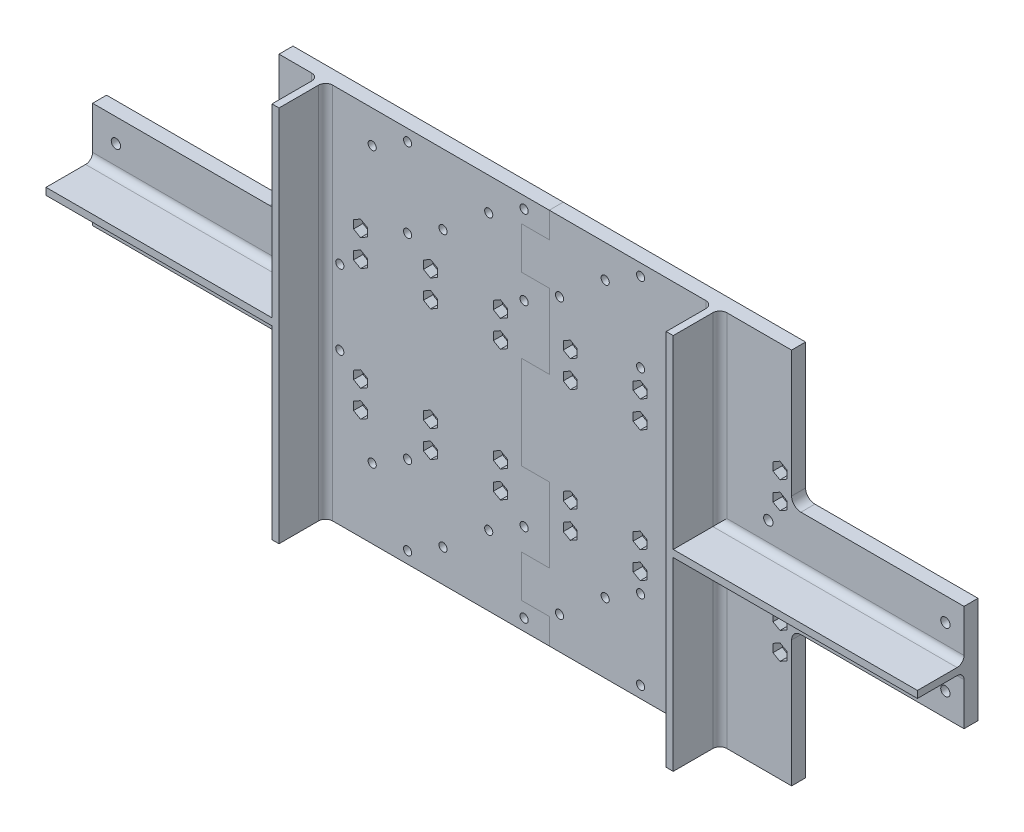
SolidWorks part; units mm, degrees
ref_plane "Top Plane" through (0, 0, 0) normal (0, 0, 1) x (1, 0, 0)
ref_plane "Right Plane" through (0, 0, 0) normal (0, 1, 0) x (1, 0, 0)
ref_plane "Front Plane" through (0, 0, 0) normal (1, 0, 0) x (0, 0, -1)
sketch "Sketch1" plane through (0, 0, 0) normal (0, 0, 1) x (1, 0, 0)
  line L0 (-187, 81) -> (187, -81) construction
  line L1 (-187, 81) -> (187, 81) construction
  line L2 (-187, 81) -> (-187, -81) construction
  line L3 (-187, -81) -> (187, -81) construction
  line L4 (187, 81) -> (187, -81) construction
  line L5 (-187, -22.75) -> (-107, -22.75) construction
  line L6 (-107, -22.75) -> (-107, -81) construction
  line L7 (113, -81) -> (113, -22.75) construction
  line L8 (113, -22.75) -> (187, -22.75) construction
  line L9 (-187, 0) -> (187, 0) construction
  line L10 (113, 22.75) -> (187, 22.75) construction
  line L11 (113, 81) -> (113, 22.75) construction
  line L12 (-107, 22.75) -> (-107, 81) construction
  line L13 (-187, 22.75) -> (-107, 22.75) construction
  line L14 (85.2, -81) -> (85.2, 81) construction
  line L15 (-93, -81) -> (-93, 81) construction
  line L16 (-187, -2.75) -> (187, -2.75) construction
  line L17 (187, 2.75) -> (-187, 2.75) construction
  text T0 "FRONT" font "Century Gothic" height in points 80
  dimension "D1" = 374
  dimension "D2" = 162
  dimension "D3" = 45.5
  dimension "D4" = 80
  dimension "D5" = 74
  dimension "D6" = 27.8
  dimension "D7" = 14
  dimension "D8" = 20
  dimension "D9" = 20
sketch "Sketch2" plane through (0, 0, 0) normal (0, 0, 1) x (1, 0, 0)
  line L0 (-187, 81) -> (-187, -81) construction
  line L1 (-187, 81) -> (187, 81) construction
  line L2 (187, 81) -> (187, -81) construction
  line L3 (-187, -81) -> (187, -81) construction
  line L4 (113, -81) -> (113, -22.75) construction
  line L5 (113, -22.75) -> (187, -22.75) construction
  line L6 (113, 22.75) -> (187, 22.75) construction
  line L7 (113, 81) -> (113, 22.75) construction
  line L8 (-107, 22.75) -> (-107, 81) construction
  line L9 (-187, 22.75) -> (-107, 22.75) construction
  line L10 (-107, -22.75) -> (-107, -81) construction
  line L11 (-187, -22.75) -> (-107, -22.75) construction
  line L12 (-187, 22.75) -> (-187, -22.75)
  line L13 (-107, 81) -> (113, 81)
  line L14 (187, 22.75) -> (187, -22.75)
  line L15 (-107, -81) -> (113, -81)
  line L16 (113, -81) -> (113, -22.75)
  line L17 (113, -22.75) -> (187, -22.75)
  line L18 (113, 22.75) -> (187, 22.75)
  line L19 (113, 81) -> (113, 22.75)
  line L20 (-107, 22.75) -> (-107, 81)
  line L21 (-187, 22.75) -> (-107, 22.75)
  line L22 (-107, -22.75) -> (-107, -81)
  line L23 (-187, -22.75) -> (-107, -22.75)
extrude "Boss-Extrude1" add sketch "Sketch2" along normal mid plane 6
sketch "Sketch3" plane through (0, 0, 3) normal (0, 0, 1) x (1, 0, 0)
  line L0 (-187, -1.5) -> (-90, -1.5)
  line L1 (-187, 81) -> (-187, -81) construction
  line L2 (187, 81) -> (187, -81) construction
  line L3 (-187, 0) -> (187, 0) construction
  line L4 (-187, 0) -> (187, 0) construction
  line L5 (-187, 1.5) -> (-90, 1.5)
  line L6 (-90, 81) -> (-90, 1.5)
  line L7 (-187, 81) -> (187, 81) construction
  line L8 (82.2, -81) -> (82.2, -1.5)
  line L9 (85.2, -81) -> (85.2, 81) construction
  line L10 (-93, -81) -> (-93, 81) construction
  line L11 (-87, -81) -> (-87, 81)
  line L12 (-187, -81) -> (187, -81) construction
  line L13 (79.2, -81) -> (79.2, 81)
  line L14 (79.2, -81) -> (82.2, -81)
  line L15 (79.2, 81) -> (82.2, 81)
  line L16 (-90, 81) -> (-87, 81)
  line L17 (-90, -81) -> (-87, -81)
  line L20 (82.2, 1.5) -> (187, 1.5)
  line L21 (82.2, -1.5) -> (187, -1.5)
  line L22 (82.2, 1.5) -> (82.2, 81)
  line L23 (-90, -1.5) -> (-90, -81)
  line L24 (187, -1.5) -> (187, 1.5)
  line L25 (-187, -1.5) -> (-187, 1.5)
  point P20 (0, 0)
  point P34 (-87, 0)
  point P35 (79.2, 0)
  dimension "D1" = 3
  dimension "D2" = 3
  dimension "D3" = 3
  dimension "D4" = 3
extrude "Boss-Extrude2" add sketch "Sketch3" along normal blind 20
sketch "Sketch4" plane through (0, 0, 3) normal (0, 0, 1) x (1, 0, 0)
  line L0 (-17, -67) -> (13.4, -67) construction
  line L1 (-67, -67) -> (-36.6, -67) construction
  line L2 (-67, -67) -> (-67, -51) construction
  line L3 (-67, -51) -> (-36.6, -51) construction
  line L4 (-36.6, -67) -> (-36.6, -51) construction
  line L5 (-17, -67) -> (-17, -51) construction
  line L6 (-17, -51) -> (13.4, -51) construction
  line L7 (13.4, -67) -> (13.4, -51) construction
  line L8 (33, -67) -> (63.4, -67) construction
  line L9 (33, -67) -> (33, -51) construction
  line L10 (33, -51) -> (63.4, -51) construction
  line L11 (63.4, -67) -> (63.4, -51) construction
  line L12 (-36.6, -67) -> (13.4, -67) construction
  line L13 (-107, -22.75) -> (-107, -81) construction
  line L14 (-67, 59) -> (63.4, 59) construction
  line L15 (-187, -81) -> (187, -81) construction
  line L16 (-187, 0) -> (187, 0) construction
  line L17 (-187, 0) -> (187, 0) construction
  line L18 (-36.6, 67) -> (13.4, 67) construction
  line L19 (63.4, 67) -> (63.4, 51) construction
  line L20 (33, 51) -> (63.4, 51) construction
  line L21 (33, 67) -> (33, 51) construction
  line L22 (33, 67) -> (63.4, 67) construction
  line L23 (13.4, 67) -> (13.4, 51) construction
  line L24 (-17, 51) -> (13.4, 51) construction
  line L25 (-17, 67) -> (-17, 51) construction
  line L26 (-36.6, 67) -> (-36.6, 51) construction
  line L27 (-67, 51) -> (-36.6, 51) construction
  line L28 (-67, 67) -> (-67, 51) construction
  line L29 (-67, 67) -> (-36.6, 67) construction
  line L30 (-17, 67) -> (13.4, 67) construction
  circle A0 centre (-36.6, -67) radius 1.75
  circle A1 centre (-67, -51) radius 1.75
  circle A2 centre (13.4, -67) radius 1.75
  circle A3 centre (-17, -51) radius 1.75
  circle A4 centre (63.4, -67) radius 1.75
  circle A5 centre (33, -51) radius 1.75
  circle A6 centre (33, 51) radius 1.75 construction
  circle A7 centre (63.4, 67) radius 1.75 construction
  circle A8 centre (-17, 51) radius 1.75 construction
  circle A9 centre (13.4, 67) radius 1.75 construction
  circle A10 centre (-67, 51) radius 1.75 construction
  circle A11 centre (-36.6, 67) radius 1.75 construction
  circle A12 centre (33, 67) radius 1.75
  circle A13 centre (63.4, 51) radius 1.75
  circle A14 centre (13.4, 51) radius 1.75
  circle A15 centre (-17, 67) radius 1.75
  circle A16 centre (-36.6, 51) radius 1.75
  circle A17 centre (-67, 67) radius 1.75
  dimension "D3" = 3.5
  dimension "D1" = 16
  dimension "D2" = 30.4
  dimension "D5" = 50
  dimension "D6" = 40
  dimension "D7" = 14
  dimension "D4" = 3
extrude "Cut-Extrude1" cut sketch "Sketch4" against normal through all
fillet "Fillet1" radius 4 4 edges at (-107, 22.75, 0) (-107, -22.75, 0) (113, -22.75, 0) (113, 22.75, 0)
fillet "Fillet2" radius 3 10 edges at (-90, 41.25, 3) (-138.5, 1.5, 3) (-138.5, -1.5, 3) (-90, -41.25, 3) (82.2, -41.25, 3) (134.6, -1.5, 3) (134.6, 1.5, 3) (82.2, 41.25, 3) (-87, 0, 3) (79.2, 0, 3)
sketch "Sketch5" plane through (0, 0, -3) normal (0, 0, -1) x (-1, 0, 0)
  circle A0 centre (-103, -12.75) radius 2 construction
  circle A1 centre (-103, 12.75) radius 2 construction
  circle A2 centre (-179, 12.75) radius 2 construction
  circle A3 centre (-179, -12.75) radius 2 construction
  circle A4 centre (177, 12.75) radius 2 construction
  circle A5 centre (177, -12.75) radius 2 construction
  circle A6 centre (101, -12.75) radius 2 construction
  circle A7 centre (101, 12.75) radius 2 construction
  circle A8 centre (-103, -12.75) radius 2
  circle A9 centre (-103, 12.75) radius 2
  circle A10 centre (-179, 12.75) radius 2
  circle A11 centre (-179, -12.75) radius 2
  circle A12 centre (177, 12.75) radius 2
  circle A13 centre (177, -12.75) radius 2
  circle A14 centre (101, -12.75) radius 2
  circle A15 centre (101, 12.75) radius 2
extrude "Cut-Extrude2" cut sketch "Sketch5" against normal up to next
sketch "Sketch6" plane through (0, 0, 3) normal (0, 0, 1) x (1, 0, 0)
  line L0 (-67, -67) -> (-36.6, -51) construction
  line L1 (-51.8, -76) -> (-51.8, -42) construction
  line L2 (-67, -59) -> (-36.6, -59) construction
  line L3 (-67, -67) -> (-67, -51) construction
  line L4 (-36.6, -67) -> (-36.6, -51) construction
  line L5 (-1.8, -76) -> (-1.8, -42) construction
  line L6 (48.2, -76) -> (48.2, -42) construction
  line L7 (-51.8, -59) -> (-1.8, -59) construction
  line L8 (-187, 0) -> (187, 0) construction
  line L9 (-187, 0) -> (187, 0) construction
  line L10 (-51.8, 59) -> (-1.8, 59) construction
  line L11 (48.2, 76) -> (48.2, 42) construction
  line L12 (-1.8, 76) -> (-1.8, 42) construction
  line L13 (-67, 59) -> (-36.6, 59) construction
  line L14 (-51.8, 76) -> (-51.8, 42) construction
  line L15 (-67, 67) -> (-36.6, 51) construction
  circle A0 centre (-51.8, -76) radius 1.75
  circle A1 centre (-51.8, -42) radius 1.75
  circle A2 centre (-1.8, -76) radius 1.75
  circle A3 centre (-1.8, -42) radius 1.75
  circle A4 centre (48.2, -76) radius 1.75
  circle A5 centre (48.2, -42) radius 1.75
  circle A6 centre (48.2, 42) radius 1.75
  circle A7 centre (48.2, 76) radius 1.75
  circle A8 centre (-1.8, 42) radius 1.75
  circle A9 centre (-1.8, 76) radius 1.75
  circle A10 centre (-51.8, 42) radius 1.75
  circle A11 centre (-51.8, 76) radius 1.75
  point P4 (-51.8, -59)
  point P17 (-1.8, -59)
  point P22 (48.2, -59)
  point P47 (48.2, 59)
  dimension "D1" = 3.5
  dimension "D2" = 34
  dimension "D4" = 50
  dimension "D3" = 3
extrude "Cut-Extrude3" cut sketch "Sketch6" against normal through all
sketch "Sketch8" plane through (0, 0, 3) normal (0, 0, 1) x (1, 0, 0)
  line L0 (-80.9, -16) -> (73.1, 16) construction
  line L1 (-80.9, -16) -> (73.1, -16) construction
  line L2 (-80.9, -16) -> (-80.9, 16) construction
  line L3 (-80.9, 16) -> (73.1, 16) construction
  line L4 (73.1, -16) -> (73.1, 16) construction
  line L5 (-187, 0) -> (187, 0) construction
  line L6 (-187, 0) -> (187, 0) construction
  line L7 (-3.9, -21.9049) -> (-3.9, 21.9049) construction
  line L8 (-93, -81) -> (85.2, 81) construction
  circle A0 centre (-80.9, -16) radius 1.75
  circle A1 centre (-80.9, 16) radius 1.75
  circle A2 centre (73.1, 16) radius 1.75
  circle A3 centre (73.1, -16) radius 1.75
  point P7 (-3.9, 0)
  dimension "D3" = 3.5
  dimension "D1" = 32
  dimension "D2" = 154
extrude "Cut-Extrude5" cut sketch "Sketch8" against normal through all
sketch "Sketch9" plane through (0, 0, 3) normal (0, 0, 1) x (1, 0, 0)
  line L0 (-107.9535, -28) -> (101.269, -28) construction
  line L1 (-12, -33.75) -> (18, -33.75) construction
  line L2 (-12, -22.25) -> (-42, -22.25) construction
  line L3 (-12, -22.25) -> (18, -22.25) construction
  line L4 (-194.5845, 0) -> (205.1662, 0) construction
  line L5 (3, -92.4344) -> (3, 92.4344) construction
  line L6 (-12, -33.75) -> (-42, -33.75) construction
  line L7 (-107, 81) -> (113, -81) construction
  line L8 (-45, -32.0179) -> (-45, -35.4821) construction
  line L9 (-15, -35.4821) -> (-12, -37.2141) construction
  line L10 (-12, -37.2141) -> (-9, -35.4821) construction
  line L11 (-9, -35.4821) -> (-9, -32.0179) construction
  line L12 (-9, -32.0179) -> (-12, -30.2859) construction
  line L13 (-12, -30.2859) -> (-15, -32.0179) construction
  line L14 (-15, -32.0179) -> (-15, -35.4821) construction
  line L15 (-45, -35.4821) -> (-42, -37.2141) construction
  line L16 (-42, -37.2141) -> (-39, -35.4821) construction
  line L17 (-39, -35.4821) -> (-39, -32.0179) construction
  line L18 (-39, -32.0179) -> (-42, -30.2859) construction
  line L19 (-42, -30.2859) -> (-45, -32.0179) construction
  line L20 (-75, -32.0179) -> (-75, -35.4821) construction
  line L21 (-75, -35.4821) -> (-72, -37.2141) construction
  line L22 (-72, -37.2141) -> (-69, -35.4821) construction
  line L23 (-69, -35.4821) -> (-69, -32.0179) construction
  line L24 (-69, -32.0179) -> (-72, -30.2859) construction
  line L25 (-72, -30.2859) -> (-75, -32.0179) construction
  line L26 (-105, -32.0179) -> (-105, -35.4821) construction
  line L27 (-105, -35.4821) -> (-102, -37.2141) construction
  line L28 (-102, -37.2141) -> (-99, -35.4821) construction
  line L29 (-99, -35.4821) -> (-99, -32.0179) construction
  line L30 (-99, -32.0179) -> (-102, -30.2859) construction
  line L31 (-102, -30.2859) -> (-105, -32.0179) construction
  line L32 (-45, -35.4821) -> (-39, -32.0179) construction
  line L33 (-42, -33.75) -> (-12, -33.75) construction
  line L34 (-12, -25.7141) -> (-15, -23.9821) construction
  line L35 (-9, -23.9821) -> (-12, -25.7141) construction
  line L36 (-9, -20.5179) -> (-9, -23.9821) construction
  line L37 (-12, -18.7859) -> (-9, -20.5179) construction
  line L38 (-15, -20.5179) -> (-12, -18.7859) construction
  line L39 (-15, -23.9821) -> (-15, -20.5179) construction
  line L40 (-39, -20.5179) -> (-39, -23.9821) construction
  line L41 (-42, -18.7859) -> (-39, -20.5179) construction
  line L42 (-45, -20.5179) -> (-42, -18.7859) construction
  line L43 (-45, -23.9821) -> (-45, -20.5179) construction
  line L44 (-42, -25.7141) -> (-45, -23.9821) construction
  line L45 (-39, -23.9821) -> (-42, -25.7141) construction
  line L46 (-69, -20.5179) -> (-69, -23.9821) construction
  line L47 (-72, -18.7859) -> (-69, -20.5179) construction
  line L48 (-75, -20.5179) -> (-72, -18.7859) construction
  line L49 (-75, -23.9821) -> (-75, -20.5179) construction
  line L50 (-72, -25.7141) -> (-75, -23.9821) construction
  line L51 (-69, -23.9821) -> (-72, -25.7141) construction
  line L52 (-99, -20.5179) -> (-99, -23.9821) construction
  line L53 (-102, -18.7859) -> (-99, -20.5179) construction
  line L54 (-105, -20.5179) -> (-102, -18.7859) construction
  line L55 (-105, -23.9821) -> (-105, -20.5179) construction
  line L56 (-102, -25.7141) -> (-105, -23.9821) construction
  line L57 (-99, -23.9821) -> (-102, -25.7141) construction
  line L58 (105, -23.9821) -> (108, -25.7141) construction
  line L59 (108, -25.7141) -> (111, -23.9821) construction
  line L60 (111, -23.9821) -> (111, -20.5179) construction
  line L61 (111, -20.5179) -> (108, -18.7859) construction
  line L62 (108, -18.7859) -> (105, -20.5179) construction
  line L63 (105, -20.5179) -> (105, -23.9821) construction
  line L64 (75, -23.9821) -> (78, -25.7141) construction
  line L65 (78, -25.7141) -> (81, -23.9821) construction
  line L66 (81, -23.9821) -> (81, -20.5179) construction
  line L67 (81, -20.5179) -> (78, -18.7859) construction
  line L68 (78, -18.7859) -> (75, -20.5179) construction
  line L69 (75, -20.5179) -> (75, -23.9821) construction
  line L70 (45, -23.9821) -> (48, -25.7141) construction
  line L71 (48, -25.7141) -> (51, -23.9821) construction
  line L72 (51, -23.9821) -> (51, -20.5179) construction
  line L73 (51, -20.5179) -> (48, -18.7859) construction
  line L74 (48, -18.7859) -> (45, -20.5179) construction
  line L75 (45, -20.5179) -> (45, -23.9821) construction
  line L76 (21, -23.9821) -> (21, -20.5179) construction
  line L77 (21, -20.5179) -> (18, -18.7859) construction
  line L78 (18, -18.7859) -> (15, -20.5179) construction
  line L79 (15, -20.5179) -> (15, -23.9821) construction
  line L80 (15, -23.9821) -> (18, -25.7141) construction
  line L81 (18, -25.7141) -> (21, -23.9821) construction
  line L82 (48, -33.75) -> (18, -33.75) construction
  line L83 (51, -35.4821) -> (45, -32.0179) construction
  line L84 (108, -30.2859) -> (111, -32.0179) construction
  line L85 (105, -32.0179) -> (108, -30.2859) construction
  line L86 (105, -35.4821) -> (105, -32.0179) construction
  line L87 (108, -37.2141) -> (105, -35.4821) construction
  line L88 (111, -35.4821) -> (108, -37.2141) construction
  line L89 (111, -32.0179) -> (111, -35.4821) construction
  line L90 (78, -30.2859) -> (81, -32.0179) construction
  line L91 (75, -32.0179) -> (78, -30.2859) construction
  line L92 (75, -35.4821) -> (75, -32.0179) construction
  line L93 (78, -37.2141) -> (75, -35.4821) construction
  line L94 (81, -35.4821) -> (78, -37.2141) construction
  line L95 (81, -32.0179) -> (81, -35.4821) construction
  line L96 (48, -30.2859) -> (51, -32.0179) construction
  line L97 (45, -32.0179) -> (48, -30.2859) construction
  line L98 (45, -35.4821) -> (45, -32.0179) construction
  line L99 (48, -37.2141) -> (45, -35.4821) construction
  line L100 (51, -35.4821) -> (48, -37.2141) construction
  line L101 (21, -32.0179) -> (21, -35.4821) construction
  line L102 (18, -30.2859) -> (21, -32.0179) construction
  line L103 (15, -32.0179) -> (18, -30.2859) construction
  line L104 (15, -35.4821) -> (15, -32.0179) construction
  line L105 (18, -37.2141) -> (15, -35.4821) construction
  line L106 (21, -35.4821) -> (18, -37.2141) construction
  line L107 (51, -32.0179) -> (51, -35.4821) construction
  line L108 (51, 32.0179) -> (51, 35.4821) construction
  line L109 (21, 35.4821) -> (18, 37.2141) construction
  line L110 (18, 37.2141) -> (15, 35.4821) construction
  line L111 (15, 35.4821) -> (15, 32.0179) construction
  line L112 (15, 32.0179) -> (18, 30.2859) construction
  line L113 (18, 30.2859) -> (21, 32.0179) construction
  line L114 (21, 32.0179) -> (21, 35.4821) construction
  line L115 (51, 35.4821) -> (48, 37.2141) construction
  line L116 (48, 37.2141) -> (45, 35.4821) construction
  line L117 (45, 35.4821) -> (45, 32.0179) construction
  line L118 (45, 32.0179) -> (48, 30.2859) construction
  line L119 (48, 30.2859) -> (51, 32.0179) construction
  line L120 (81, 32.0179) -> (81, 35.4821) construction
  line L121 (81, 35.4821) -> (78, 37.2141) construction
  line L122 (78, 37.2141) -> (75, 35.4821) construction
  line L123 (75, 35.4821) -> (75, 32.0179) construction
  line L124 (75, 32.0179) -> (78, 30.2859) construction
  line L125 (78, 30.2859) -> (81, 32.0179) construction
  line L126 (111, 32.0179) -> (111, 35.4821) construction
  line L127 (111, 35.4821) -> (108, 37.2141) construction
  line L128 (108, 37.2141) -> (105, 35.4821) construction
  line L129 (105, 35.4821) -> (105, 32.0179) construction
  line L130 (105, 32.0179) -> (108, 30.2859) construction
  line L131 (108, 30.2859) -> (111, 32.0179) construction
  line L132 (51, 35.4821) -> (45, 32.0179) construction
  line L133 (48, 33.75) -> (18, 33.75) construction
  line L134 (18, 25.7141) -> (21, 23.9821) construction
  line L135 (15, 23.9821) -> (18, 25.7141) construction
  line L136 (15, 20.5179) -> (15, 23.9821) construction
  line L137 (18, 18.7859) -> (15, 20.5179) construction
  line L138 (21, 20.5179) -> (18, 18.7859) construction
  line L139 (21, 23.9821) -> (21, 20.5179) construction
  line L140 (45, 20.5179) -> (45, 23.9821) construction
  line L141 (48, 18.7859) -> (45, 20.5179) construction
  line L142 (51, 20.5179) -> (48, 18.7859) construction
  line L143 (51, 23.9821) -> (51, 20.5179) construction
  line L144 (48, 25.7141) -> (51, 23.9821) construction
  line L145 (45, 23.9821) -> (48, 25.7141) construction
  line L146 (75, 20.5179) -> (75, 23.9821) construction
  line L147 (78, 18.7859) -> (75, 20.5179) construction
  line L148 (81, 20.5179) -> (78, 18.7859) construction
  line L149 (81, 23.9821) -> (81, 20.5179) construction
  line L150 (78, 25.7141) -> (81, 23.9821) construction
  line L151 (75, 23.9821) -> (78, 25.7141) construction
  line L152 (105, 20.5179) -> (105, 23.9821) construction
  line L153 (108, 18.7859) -> (105, 20.5179) construction
  line L154 (111, 20.5179) -> (108, 18.7859) construction
  line L155 (111, 23.9821) -> (111, 20.5179) construction
  line L156 (108, 25.7141) -> (111, 23.9821) construction
  line L157 (105, 23.9821) -> (108, 25.7141) construction
  line L158 (-99, 23.9821) -> (-102, 25.7141) construction
  line L159 (-102, 25.7141) -> (-105, 23.9821) construction
  line L160 (-105, 23.9821) -> (-105, 20.5179) construction
  line L161 (-105, 20.5179) -> (-102, 18.7859) construction
  line L162 (-102, 18.7859) -> (-99, 20.5179) construction
  line L163 (-99, 20.5179) -> (-99, 23.9821) construction
  line L164 (-69, 23.9821) -> (-72, 25.7141) construction
  line L165 (-72, 25.7141) -> (-75, 23.9821) construction
  line L166 (-75, 23.9821) -> (-75, 20.5179) construction
  line L167 (-75, 20.5179) -> (-72, 18.7859) construction
  line L168 (-72, 18.7859) -> (-69, 20.5179) construction
  line L169 (-69, 20.5179) -> (-69, 23.9821) construction
  line L170 (-39, 23.9821) -> (-42, 25.7141) construction
  line L171 (-42, 25.7141) -> (-45, 23.9821) construction
  line L172 (-45, 23.9821) -> (-45, 20.5179) construction
  line L173 (-45, 20.5179) -> (-42, 18.7859) construction
  line L174 (-42, 18.7859) -> (-39, 20.5179) construction
  line L175 (-39, 20.5179) -> (-39, 23.9821) construction
  line L176 (-15, 23.9821) -> (-15, 20.5179) construction
  line L177 (-15, 20.5179) -> (-12, 18.7859) construction
  line L178 (-12, 18.7859) -> (-9, 20.5179) construction
  line L179 (-9, 20.5179) -> (-9, 23.9821) construction
  line L180 (-9, 23.9821) -> (-12, 25.7141) construction
  line L181 (-12, 25.7141) -> (-15, 23.9821) construction
  line L182 (-42, 33.75) -> (-12, 33.75) construction
  line L183 (-45, 35.4821) -> (-39, 32.0179) construction
  line L184 (-102, 30.2859) -> (-105, 32.0179) construction
  line L185 (-99, 32.0179) -> (-102, 30.2859) construction
  line L186 (-99, 35.4821) -> (-99, 32.0179) construction
  line L187 (-102, 37.2141) -> (-99, 35.4821) construction
  line L188 (-105, 35.4821) -> (-102, 37.2141) construction
  line L189 (-105, 32.0179) -> (-105, 35.4821) construction
  line L190 (-72, 30.2859) -> (-75, 32.0179) construction
  line L191 (-69, 32.0179) -> (-72, 30.2859) construction
  line L192 (-69, 35.4821) -> (-69, 32.0179) construction
  line L193 (-72, 37.2141) -> (-69, 35.4821) construction
  line L194 (-75, 35.4821) -> (-72, 37.2141) construction
  line L195 (-75, 32.0179) -> (-75, 35.4821) construction
  line L196 (-42, 30.2859) -> (-45, 32.0179) construction
  line L197 (-39, 32.0179) -> (-42, 30.2859) construction
  line L198 (-39, 35.4821) -> (-39, 32.0179) construction
  line L199 (-42, 37.2141) -> (-39, 35.4821) construction
  line L200 (-45, 35.4821) -> (-42, 37.2141) construction
  line L201 (-15, 32.0179) -> (-15, 35.4821) construction
  line L202 (-12, 30.2859) -> (-15, 32.0179) construction
  line L203 (-9, 32.0179) -> (-12, 30.2859) construction
  line L204 (-9, 35.4821) -> (-9, 32.0179) construction
  line L205 (-12, 37.2141) -> (-9, 35.4821) construction
  line L206 (-15, 35.4821) -> (-12, 37.2141) construction
  line L207 (-45, 32.0179) -> (-45, 35.4821) construction
  line L208 (-12, 33.75) -> (-42, 33.75) construction
  line L209 (-12, 22.25) -> (18, 22.25) construction
  line L210 (-12, 22.25) -> (-42, 22.25) construction
  line L211 (-12, 33.75) -> (18, 33.75) construction
  line L212 (-107.9535, 28) -> (101.269, 28) construction
  circle A0 centre (-12, -33.75) radius 1.75
  circle A1 centre (-42, -33.75) radius 1.75
  circle A2 centre (-72, -33.75) radius 1.75
  circle A3 centre (-102, -33.75) radius 1.75
  circle A4 centre (108, -33.75) radius 1.75
  circle A5 centre (78, -33.75) radius 1.75 construction
  circle A6 centre (48, -33.75) radius 1.75
  circle A7 centre (18, -33.75) radius 1.75
  circle A8 centre (18, -22.25) radius 1.75
  circle A9 centre (48, -22.25) radius 1.75
  circle A10 centre (78, -22.25) radius 1.75 construction
  circle A11 centre (108, -22.25) radius 1.75
  circle A12 centre (-102, -22.25) radius 1.75
  circle A13 centre (-72, -22.25) radius 1.75
  circle A14 centre (-42, -22.25) radius 1.75
  circle A15 centre (-12, -22.25) radius 1.75
  circle A16 centre (-12, -33.75) radius 3 construction
  circle A17 centre (-12, 33.75) radius 3 construction
  circle A18 centre (-12, 22.25) radius 1.75
  circle A19 centre (-42, 22.25) radius 1.75
  circle A20 centre (-72, 22.25) radius 1.75
  circle A21 centre (-102, 22.25) radius 1.75
  circle A22 centre (108, 22.25) radius 1.75
  circle A23 centre (78, 22.25) radius 1.75 construction
  circle A24 centre (48, 22.25) radius 1.75
  circle A25 centre (18, 22.25) radius 1.75
  circle A26 centre (18, 33.75) radius 1.75
  circle A27 centre (48, 33.75) radius 1.75
  circle A28 centre (78, 33.75) radius 1.75 construction
  circle A29 centre (108, 33.75) radius 1.75
  circle A30 centre (-102, 33.75) radius 1.75
  circle A31 centre (-72, 33.75) radius 1.75
  circle A32 centre (-42, 33.75) radius 1.75
  circle A33 centre (-12, 33.75) radius 1.75
  point P6 (3, -33.75)
  point P39 (3, -22.25)
  point P46 (3, 0)
  point P277 (3, 22.25)
  point P278 (3, 33.75)
  dimension "D3" = 3.5
  dimension "D1" = 11.5
  dimension "D2" = 28
  dimension "D5" = 30
  dimension "D6" = 6
  dimension "D4" = 4
  dimension "D7" = 4
extrude "Cut-Extrude6" cut sketch "Sketch9" against normal through all
sketch "Sketch10" plane through (0, 0, 3) normal (0, 0, 1) x (1, 0, 0)
  line L0 (-99, -35.4821) -> (-99, -32.0179) construction
  line L1 (-102, -37.2141) -> (-99, -35.4821) construction
  line L2 (-105, -35.4821) -> (-102, -37.2141) construction
  line L3 (-105, -32.0179) -> (-105, -35.4821) construction
  line L4 (-102, -30.2859) -> (-105, -32.0179) construction
  line L5 (-99, -32.0179) -> (-102, -30.2859) construction
  line L6 (-99, -35.4821) -> (-99, -32.0179)
  line L7 (-102, -37.2141) -> (-99, -35.4821)
  line L8 (-105, -35.4821) -> (-102, -37.2141)
  line L9 (-105, -32.0179) -> (-105, -35.4821)
  line L10 (-102, -30.2859) -> (-105, -32.0179)
  line L11 (-99, -32.0179) -> (-102, -30.2859)
  line L12 (-69, -35.4821) -> (-69, -32.0179) construction
  line L13 (-72, -37.2141) -> (-69, -35.4821) construction
  line L14 (-75, -35.4821) -> (-72, -37.2141) construction
  line L15 (-75, -32.0179) -> (-75, -35.4821) construction
  line L16 (-72, -30.2859) -> (-75, -32.0179) construction
  line L17 (-69, -32.0179) -> (-72, -30.2859) construction
  line L18 (-69, -35.4821) -> (-69, -32.0179)
  line L19 (-72, -37.2141) -> (-69, -35.4821)
  line L20 (-75, -35.4821) -> (-72, -37.2141)
  line L21 (-75, -32.0179) -> (-75, -35.4821)
  line L22 (-72, -30.2859) -> (-75, -32.0179)
  line L23 (-69, -32.0179) -> (-72, -30.2859)
  line L24 (-39, -35.4821) -> (-39, -32.0179) construction
  line L25 (-42, -37.2141) -> (-39, -35.4821) construction
  line L26 (-45, -35.4821) -> (-42, -37.2141) construction
  line L27 (-45, -32.0179) -> (-45, -35.4821) construction
  line L28 (-42, -30.2859) -> (-45, -32.0179) construction
  line L29 (-39, -32.0179) -> (-42, -30.2859) construction
  line L30 (-39, -35.4821) -> (-39, -32.0179)
  line L31 (-42, -37.2141) -> (-39, -35.4821)
  line L32 (-45, -35.4821) -> (-42, -37.2141)
  line L33 (-45, -32.0179) -> (-45, -35.4821)
  line L34 (-42, -30.2859) -> (-45, -32.0179)
  line L35 (-39, -32.0179) -> (-42, -30.2859)
  line L36 (-9, -35.4821) -> (-9, -32.0179) construction
  line L37 (-12, -37.2141) -> (-9, -35.4821) construction
  line L38 (-15, -35.4821) -> (-12, -37.2141) construction
  line L39 (-15, -32.0179) -> (-15, -35.4821) construction
  line L40 (-12, -30.2859) -> (-15, -32.0179) construction
  line L41 (-9, -32.0179) -> (-12, -30.2859) construction
  line L42 (-9, -35.4821) -> (-9, -32.0179)
  line L43 (-12, -37.2141) -> (-9, -35.4821)
  line L44 (-15, -35.4821) -> (-12, -37.2141)
  line L45 (-15, -32.0179) -> (-15, -35.4821)
  line L46 (-12, -30.2859) -> (-15, -32.0179)
  line L47 (-9, -32.0179) -> (-12, -30.2859)
  line L48 (75, -35.4821) -> (75, -32.0179) construction
  line L49 (78, -37.2141) -> (75, -35.4821) construction
  line L50 (81, -35.4821) -> (78, -37.2141) construction
  line L51 (81, -32.0179) -> (81, -35.4821) construction
  line L52 (78, -30.2859) -> (81, -32.0179) construction
  line L53 (75, -32.0179) -> (78, -30.2859) construction
  line L54 (51, -32.0179) -> (51, -35.4821) construction
  line L55 (48, -30.2859) -> (51, -32.0179) construction
  line L56 (45, -32.0179) -> (48, -30.2859) construction
  line L57 (15, -32.0179) -> (18, -30.2859) construction
  line L58 (15, -35.4821) -> (15, -32.0179) construction
  line L59 (18, -37.2141) -> (15, -35.4821) construction
  line L60 (21, -35.4821) -> (18, -37.2141) construction
  line L61 (21, -32.0179) -> (21, -35.4821) construction
  line L62 (18, -30.2859) -> (21, -32.0179) construction
  line L63 (75, -35.4821) -> (75, -32.0179) construction
  line L64 (78, -37.2141) -> (75, -35.4821) construction
  line L65 (81, -35.4821) -> (78, -37.2141) construction
  line L66 (81, -32.0179) -> (81, -35.4821) construction
  line L67 (78, -30.2859) -> (81, -32.0179) construction
  line L68 (75, -32.0179) -> (78, -30.2859) construction
  line L69 (51, -32.0179) -> (51, -35.4821)
  line L70 (48, -30.2859) -> (51, -32.0179)
  line L71 (45, -32.0179) -> (48, -30.2859)
  line L72 (15, -32.0179) -> (18, -30.2859)
  line L73 (15, -35.4821) -> (15, -32.0179)
  line L74 (18, -37.2141) -> (15, -35.4821)
  line L75 (21, -35.4821) -> (18, -37.2141)
  line L76 (21, -32.0179) -> (21, -35.4821)
  line L77 (18, -30.2859) -> (21, -32.0179)
  line L78 (45, -35.4821) -> (45, -32.0179) construction
  line L79 (48, -37.2141) -> (45, -35.4821) construction
  line L80 (51, -35.4821) -> (48, -37.2141) construction
  line L81 (45, -35.4821) -> (45, -32.0179)
  line L82 (48, -37.2141) -> (45, -35.4821)
  line L83 (51, -35.4821) -> (48, -37.2141)
  line L84 (51, -23.9821) -> (51, -20.5179) construction
  line L85 (48, -25.7141) -> (51, -23.9821) construction
  line L86 (45, -23.9821) -> (48, -25.7141) construction
  line L87 (45, -20.5179) -> (45, -23.9821) construction
  line L88 (48, -18.7859) -> (45, -20.5179) construction
  line L89 (51, -20.5179) -> (48, -18.7859) construction
  line L90 (81, -20.5179) -> (78, -18.7859) construction
  line L91 (81, -23.9821) -> (81, -20.5179) construction
  line L92 (78, -25.7141) -> (81, -23.9821) construction
  line L93 (75, -23.9821) -> (78, -25.7141) construction
  line L94 (75, -20.5179) -> (75, -23.9821) construction
  line L95 (78, -18.7859) -> (75, -20.5179) construction
  line L96 (105, -23.9821) -> (108, -25.7141) construction
  line L97 (105, -20.5179) -> (105, -23.9821) construction
  line L98 (108, -18.7859) -> (105, -20.5179) construction
  line L99 (111, -20.5179) -> (108, -18.7859) construction
  line L100 (111, -23.9821) -> (111, -20.5179) construction
  line L101 (108, -25.7141) -> (111, -23.9821) construction
  line L102 (105, -32.0179) -> (108, -30.2859) construction
  line L103 (105, -35.4821) -> (105, -32.0179) construction
  line L104 (108, -37.2141) -> (105, -35.4821) construction
  line L105 (111, -35.4821) -> (108, -37.2141) construction
  line L106 (111, -32.0179) -> (111, -35.4821) construction
  line L107 (108, -30.2859) -> (111, -32.0179) construction
  line L108 (51, -23.9821) -> (51, -20.5179)
  line L109 (48, -25.7141) -> (51, -23.9821)
  line L110 (45, -23.9821) -> (48, -25.7141)
  line L111 (45, -20.5179) -> (45, -23.9821)
  line L112 (48, -18.7859) -> (45, -20.5179)
  line L113 (51, -20.5179) -> (48, -18.7859)
  line L114 (81, -20.5179) -> (78, -18.7859) construction
  line L115 (81, -23.9821) -> (81, -20.5179) construction
  line L116 (78, -25.7141) -> (81, -23.9821) construction
  line L117 (75, -23.9821) -> (78, -25.7141) construction
  line L118 (75, -20.5179) -> (75, -23.9821) construction
  line L119 (78, -18.7859) -> (75, -20.5179) construction
  line L120 (105, -23.9821) -> (108, -25.7141)
  line L121 (105, -20.5179) -> (105, -23.9821)
  line L122 (108, -18.7859) -> (105, -20.5179)
  line L123 (111, -20.5179) -> (108, -18.7859)
  line L124 (111, -23.9821) -> (111, -20.5179)
  line L125 (108, -25.7141) -> (111, -23.9821)
  line L126 (105, -32.0179) -> (108, -30.2859)
  line L127 (105, -35.4821) -> (105, -32.0179)
  line L128 (108, -37.2141) -> (105, -35.4821)
  line L129 (111, -35.4821) -> (108, -37.2141)
  line L130 (111, -32.0179) -> (111, -35.4821)
  line L131 (108, -30.2859) -> (111, -32.0179)
  line L132 (-45, -20.5179) -> (-42, -18.7859) construction
  line L133 (-45, -23.9821) -> (-45, -20.5179) construction
  line L134 (-42, -25.7141) -> (-45, -23.9821) construction
  line L135 (-39, -23.9821) -> (-42, -25.7141) construction
  line L136 (-39, -20.5179) -> (-39, -23.9821) construction
  line L137 (-42, -18.7859) -> (-39, -20.5179) construction
  line L138 (-15, -20.5179) -> (-12, -18.7859) construction
  line L139 (-15, -23.9821) -> (-15, -20.5179) construction
  line L140 (-12, -25.7141) -> (-15, -23.9821) construction
  line L141 (-9, -23.9821) -> (-12, -25.7141) construction
  line L142 (-9, -20.5179) -> (-9, -23.9821) construction
  line L143 (-12, -18.7859) -> (-9, -20.5179) construction
  line L144 (21, -20.5179) -> (18, -18.7859) construction
  line L145 (21, -23.9821) -> (21, -20.5179) construction
  line L146 (18, -25.7141) -> (21, -23.9821) construction
  line L147 (15, -23.9821) -> (18, -25.7141) construction
  line L148 (15, -20.5179) -> (15, -23.9821) construction
  line L149 (18, -18.7859) -> (15, -20.5179) construction
  line L150 (-45, -20.5179) -> (-42, -18.7859)
  line L151 (-45, -23.9821) -> (-45, -20.5179)
  line L152 (-42, -25.7141) -> (-45, -23.9821)
  line L153 (-39, -23.9821) -> (-42, -25.7141)
  line L154 (-39, -20.5179) -> (-39, -23.9821)
  line L155 (-42, -18.7859) -> (-39, -20.5179)
  line L156 (-15, -20.5179) -> (-12, -18.7859)
  line L157 (-15, -23.9821) -> (-15, -20.5179)
  line L158 (-12, -25.7141) -> (-15, -23.9821)
  line L159 (-9, -23.9821) -> (-12, -25.7141)
  line L160 (-9, -20.5179) -> (-9, -23.9821)
  line L161 (-12, -18.7859) -> (-9, -20.5179)
  line L162 (21, -20.5179) -> (18, -18.7859)
  line L163 (21, -23.9821) -> (21, -20.5179)
  line L164 (18, -25.7141) -> (21, -23.9821)
  line L165 (15, -23.9821) -> (18, -25.7141)
  line L166 (15, -20.5179) -> (15, -23.9821)
  line L167 (18, -18.7859) -> (15, -20.5179)
  line L168 (-105, -23.9821) -> (-105, -20.5179) construction
  line L169 (-102, -25.7141) -> (-105, -23.9821) construction
  line L170 (-99, -23.9821) -> (-102, -25.7141) construction
  line L171 (-99, -20.5179) -> (-99, -23.9821) construction
  line L172 (-102, -18.7859) -> (-99, -20.5179) construction
  line L173 (-105, -20.5179) -> (-102, -18.7859) construction
  line L174 (-72, -25.7141) -> (-75, -23.9821) construction
  line L175 (-69, -23.9821) -> (-72, -25.7141) construction
  line L176 (-69, -20.5179) -> (-69, -23.9821) construction
  line L177 (-72, -18.7859) -> (-69, -20.5179) construction
  line L178 (-75, -20.5179) -> (-72, -18.7859) construction
  line L179 (-75, -23.9821) -> (-75, -20.5179) construction
  line L180 (-105, -23.9821) -> (-105, -20.5179)
  line L181 (-102, -25.7141) -> (-105, -23.9821)
  line L182 (-99, -23.9821) -> (-102, -25.7141)
  line L183 (-99, -20.5179) -> (-99, -23.9821)
  line L184 (-102, -18.7859) -> (-99, -20.5179)
  line L185 (-105, -20.5179) -> (-102, -18.7859)
  line L186 (-72, -25.7141) -> (-75, -23.9821)
  line L187 (-69, -23.9821) -> (-72, -25.7141)
  line L188 (-69, -20.5179) -> (-69, -23.9821)
  line L189 (-72, -18.7859) -> (-69, -20.5179)
  line L190 (-75, -20.5179) -> (-72, -18.7859)
  line L191 (-75, -23.9821) -> (-75, -20.5179)
  line L192 (-69, 20.5179) -> (-69, 23.9821) construction
  line L193 (-72, 18.7859) -> (-69, 20.5179) construction
  line L194 (-75, 20.5179) -> (-72, 18.7859) construction
  line L195 (-75, 23.9821) -> (-75, 20.5179) construction
  line L196 (-72, 25.7141) -> (-75, 23.9821) construction
  line L197 (-69, 23.9821) -> (-72, 25.7141) construction
  line L198 (-75, 35.4821) -> (-72, 37.2141) construction
  line L199 (-75, 32.0179) -> (-75, 35.4821) construction
  line L200 (-72, 30.2859) -> (-75, 32.0179) construction
  line L201 (-69, 32.0179) -> (-72, 30.2859) construction
  line L202 (-69, 35.4821) -> (-69, 32.0179) construction
  line L203 (-72, 37.2141) -> (-69, 35.4821) construction
  line L204 (-99, 20.5179) -> (-99, 23.9821) construction
  line L205 (-102, 18.7859) -> (-99, 20.5179) construction
  line L206 (-105, 20.5179) -> (-102, 18.7859) construction
  line L207 (-105, 23.9821) -> (-105, 20.5179) construction
  line L208 (-102, 25.7141) -> (-105, 23.9821) construction
  line L209 (-99, 23.9821) -> (-102, 25.7141) construction
  line L210 (-105, 35.4821) -> (-102, 37.2141) construction
  line L211 (-105, 32.0179) -> (-105, 35.4821) construction
  line L212 (-102, 30.2859) -> (-105, 32.0179) construction
  line L213 (-99, 32.0179) -> (-102, 30.2859) construction
  line L214 (-99, 35.4821) -> (-99, 32.0179) construction
  line L215 (-102, 37.2141) -> (-99, 35.4821) construction
  line L216 (-69, 20.5179) -> (-69, 23.9821)
  line L217 (-72, 18.7859) -> (-69, 20.5179)
  line L218 (-75, 20.5179) -> (-72, 18.7859)
  line L219 (-75, 23.9821) -> (-75, 20.5179)
  line L220 (-72, 25.7141) -> (-75, 23.9821)
  line L221 (-69, 23.9821) -> (-72, 25.7141)
  line L222 (-75, 35.4821) -> (-72, 37.2141)
  line L223 (-75, 32.0179) -> (-75, 35.4821)
  line L224 (-72, 30.2859) -> (-75, 32.0179)
  line L225 (-69, 32.0179) -> (-72, 30.2859)
  line L226 (-69, 35.4821) -> (-69, 32.0179)
  line L227 (-72, 37.2141) -> (-69, 35.4821)
  line L228 (-99, 20.5179) -> (-99, 23.9821)
  line L229 (-102, 18.7859) -> (-99, 20.5179)
  line L230 (-105, 20.5179) -> (-102, 18.7859)
  line L231 (-105, 23.9821) -> (-105, 20.5179)
  line L232 (-102, 25.7141) -> (-105, 23.9821)
  line L233 (-99, 23.9821) -> (-102, 25.7141)
  line L234 (-105, 35.4821) -> (-102, 37.2141)
  line L235 (-105, 32.0179) -> (-105, 35.4821)
  line L236 (-102, 30.2859) -> (-105, 32.0179)
  line L237 (-99, 32.0179) -> (-102, 30.2859)
  line L238 (-99, 35.4821) -> (-99, 32.0179)
  line L239 (-102, 37.2141) -> (-99, 35.4821)
  line L240 (-12, 18.7859) -> (-9, 20.5179) construction
  line L241 (-15, 20.5179) -> (-12, 18.7859) construction
  line L242 (-15, 23.9821) -> (-15, 20.5179) construction
  line L243 (-12, 25.7141) -> (-15, 23.9821) construction
  line L244 (-9, 23.9821) -> (-12, 25.7141) construction
  line L245 (-9, 20.5179) -> (-9, 23.9821) construction
  line L246 (-15, 35.4821) -> (-12, 37.2141) construction
  line L247 (-15, 32.0179) -> (-15, 35.4821) construction
  line L248 (-12, 30.2859) -> (-15, 32.0179) construction
  line L249 (-9, 32.0179) -> (-12, 30.2859) construction
  line L250 (-9, 35.4821) -> (-9, 32.0179) construction
  line L251 (-12, 37.2141) -> (-9, 35.4821) construction
  line L252 (-39, 20.5179) -> (-39, 23.9821) construction
  line L253 (-42, 18.7859) -> (-39, 20.5179) construction
  line L254 (-45, 20.5179) -> (-42, 18.7859) construction
  line L255 (-45, 23.9821) -> (-45, 20.5179) construction
  line L256 (-42, 25.7141) -> (-45, 23.9821) construction
  line L257 (-39, 23.9821) -> (-42, 25.7141) construction
  line L258 (-45, 32.0179) -> (-45, 35.4821) construction
  line L259 (-42, 30.2859) -> (-45, 32.0179) construction
  line L260 (-39, 32.0179) -> (-42, 30.2859) construction
  line L261 (-39, 35.4821) -> (-39, 32.0179) construction
  line L262 (-42, 37.2141) -> (-39, 35.4821) construction
  line L263 (-45, 35.4821) -> (-42, 37.2141) construction
  line L264 (-12, 18.7859) -> (-9, 20.5179)
  line L265 (-15, 20.5179) -> (-12, 18.7859)
  line L266 (-15, 23.9821) -> (-15, 20.5179)
  line L267 (-12, 25.7141) -> (-15, 23.9821)
  line L268 (-9, 23.9821) -> (-12, 25.7141)
  line L269 (-9, 20.5179) -> (-9, 23.9821)
  line L270 (-15, 35.4821) -> (-12, 37.2141)
  line L271 (-15, 32.0179) -> (-15, 35.4821)
  line L272 (-12, 30.2859) -> (-15, 32.0179)
  line L273 (-9, 32.0179) -> (-12, 30.2859)
  line L274 (-9, 35.4821) -> (-9, 32.0179)
  line L275 (-12, 37.2141) -> (-9, 35.4821)
  line L276 (-39, 20.5179) -> (-39, 23.9821)
  line L277 (-42, 18.7859) -> (-39, 20.5179)
  line L278 (-45, 20.5179) -> (-42, 18.7859)
  line L279 (-45, 23.9821) -> (-45, 20.5179)
  line L280 (-42, 25.7141) -> (-45, 23.9821)
  line L281 (-39, 23.9821) -> (-42, 25.7141)
  line L282 (-45, 32.0179) -> (-45, 35.4821)
  line L283 (-42, 30.2859) -> (-45, 32.0179)
  line L284 (-39, 32.0179) -> (-42, 30.2859)
  line L285 (-39, 35.4821) -> (-39, 32.0179)
  line L286 (-42, 37.2141) -> (-39, 35.4821)
  line L287 (-45, 35.4821) -> (-42, 37.2141)
  line L288 (45, 23.9821) -> (48, 25.7141) construction
  line L289 (45, 20.5179) -> (45, 23.9821) construction
  line L290 (48, 18.7859) -> (45, 20.5179) construction
  line L291 (51, 20.5179) -> (48, 18.7859) construction
  line L292 (51, 23.9821) -> (51, 20.5179) construction
  line L293 (48, 25.7141) -> (51, 23.9821) construction
  line L294 (51, 32.0179) -> (51, 35.4821) construction
  line L295 (48, 30.2859) -> (51, 32.0179) construction
  line L296 (45, 32.0179) -> (48, 30.2859) construction
  line L297 (45, 35.4821) -> (45, 32.0179) construction
  line L298 (48, 37.2141) -> (45, 35.4821) construction
  line L299 (51, 35.4821) -> (48, 37.2141) construction
  line L300 (15, 23.9821) -> (18, 25.7141) construction
  line L301 (15, 20.5179) -> (15, 23.9821) construction
  line L302 (18, 18.7859) -> (15, 20.5179) construction
  line L303 (21, 20.5179) -> (18, 18.7859) construction
  line L304 (21, 23.9821) -> (21, 20.5179) construction
  line L305 (18, 25.7141) -> (21, 23.9821) construction
  line L306 (21, 32.0179) -> (21, 35.4821) construction
  line L307 (18, 30.2859) -> (21, 32.0179) construction
  line L308 (15, 32.0179) -> (18, 30.2859) construction
  line L309 (15, 35.4821) -> (15, 32.0179) construction
  line L310 (18, 37.2141) -> (15, 35.4821) construction
  line L311 (21, 35.4821) -> (18, 37.2141) construction
  line L312 (45, 23.9821) -> (48, 25.7141)
  line L313 (45, 20.5179) -> (45, 23.9821)
  line L314 (48, 18.7859) -> (45, 20.5179)
  line L315 (51, 20.5179) -> (48, 18.7859)
  line L316 (51, 23.9821) -> (51, 20.5179)
  line L317 (48, 25.7141) -> (51, 23.9821)
  line L318 (51, 32.0179) -> (51, 35.4821)
  line L319 (48, 30.2859) -> (51, 32.0179)
  line L320 (45, 32.0179) -> (48, 30.2859)
  line L321 (45, 35.4821) -> (45, 32.0179)
  line L322 (48, 37.2141) -> (45, 35.4821)
  line L323 (51, 35.4821) -> (48, 37.2141)
  line L324 (15, 23.9821) -> (18, 25.7141)
  line L325 (15, 20.5179) -> (15, 23.9821)
  line L326 (18, 18.7859) -> (15, 20.5179)
  line L327 (21, 20.5179) -> (18, 18.7859)
  line L328 (21, 23.9821) -> (21, 20.5179)
  line L329 (18, 25.7141) -> (21, 23.9821)
  line L330 (21, 32.0179) -> (21, 35.4821)
  line L331 (18, 30.2859) -> (21, 32.0179)
  line L332 (15, 32.0179) -> (18, 30.2859)
  line L333 (15, 35.4821) -> (15, 32.0179)
  line L334 (18, 37.2141) -> (15, 35.4821)
  line L335 (21, 35.4821) -> (18, 37.2141)
  line L336 (105, 23.9821) -> (108, 25.7141) construction
  line L337 (105, 20.5179) -> (105, 23.9821) construction
  line L338 (108, 18.7859) -> (105, 20.5179) construction
  line L339 (111, 20.5179) -> (108, 18.7859) construction
  line L340 (111, 23.9821) -> (111, 20.5179) construction
  line L341 (108, 25.7141) -> (111, 23.9821) construction
  line L342 (111, 32.0179) -> (111, 35.4821) construction
  line L343 (108, 30.2859) -> (111, 32.0179) construction
  line L344 (105, 32.0179) -> (108, 30.2859) construction
  line L345 (105, 35.4821) -> (105, 32.0179) construction
  line L346 (108, 37.2141) -> (105, 35.4821) construction
  line L347 (111, 35.4821) -> (108, 37.2141) construction
  line L348 (75, 23.9821) -> (78, 25.7141) construction
  line L349 (75, 20.5179) -> (75, 23.9821) construction
  line L350 (78, 18.7859) -> (75, 20.5179) construction
  line L351 (81, 20.5179) -> (78, 18.7859) construction
  line L352 (81, 23.9821) -> (81, 20.5179) construction
  line L353 (78, 25.7141) -> (81, 23.9821) construction
  line L354 (81, 32.0179) -> (81, 35.4821) construction
  line L355 (78, 30.2859) -> (81, 32.0179) construction
  line L356 (75, 32.0179) -> (78, 30.2859) construction
  line L357 (75, 35.4821) -> (75, 32.0179) construction
  line L358 (78, 37.2141) -> (75, 35.4821) construction
  line L359 (81, 35.4821) -> (78, 37.2141) construction
  line L360 (105, 23.9821) -> (108, 25.7141)
  line L361 (105, 20.5179) -> (105, 23.9821)
  line L362 (108, 18.7859) -> (105, 20.5179)
  line L363 (111, 20.5179) -> (108, 18.7859)
  line L364 (111, 23.9821) -> (111, 20.5179)
  line L365 (108, 25.7141) -> (111, 23.9821)
  line L366 (111, 32.0179) -> (111, 35.4821)
  line L367 (108, 30.2859) -> (111, 32.0179)
  line L368 (105, 32.0179) -> (108, 30.2859)
  line L369 (105, 35.4821) -> (105, 32.0179)
  line L370 (108, 37.2141) -> (105, 35.4821)
  line L371 (111, 35.4821) -> (108, 37.2141)
  line L372 (75, 23.9821) -> (78, 25.7141) construction
  line L373 (75, 20.5179) -> (75, 23.9821) construction
  line L374 (78, 18.7859) -> (75, 20.5179) construction
  line L375 (81, 20.5179) -> (78, 18.7859) construction
  line L376 (81, 23.9821) -> (81, 20.5179) construction
  line L377 (78, 25.7141) -> (81, 23.9821) construction
  line L378 (81, 32.0179) -> (81, 35.4821) construction
  line L379 (78, 30.2859) -> (81, 32.0179) construction
  line L380 (75, 32.0179) -> (78, 30.2859) construction
  line L381 (75, 35.4821) -> (75, 32.0179) construction
  line L382 (78, 37.2141) -> (75, 35.4821) construction
  line L383 (81, 35.4821) -> (78, 37.2141) construction
extrude "Cut-Extrude7" cut sketch "Sketch10" against normal blind 4
sketch "Sketch11" plane through (0, 0, 3) normal (0, 0, 1) x (1, 0, 0)
  line L0 (9, -81) -> (9, -20) construction
  line L1 (-187, -81) -> (187, -81) construction
  line L2 (9, -20) -> (-3, -20)
  line L3 (-3, -20) -> (-3, 20)
  line L4 (-187, 0) -> (187, 0) construction
  line L5 (-187, 0) -> (187, 0) construction
  line L6 (9, 20) -> (-3, 20)
  line L7 (9, 81) -> (9, 20) construction
  line L8 (-107, -81) -> (113, 81) construction
  line L9 (3, -88.9916) -> (3, 88.9916) construction
  line L10 (9, -70) -> (-3, -70)
  line L11 (-3, 11.7468) -> (3, 11.7468) construction
  line L12 (3, 17.6937) -> (9, 17.6937) construction
  line L13 (-3, -70) -> (-3, -52)
  line L14 (-3, -52) -> (9, -52)
  line L15 (9, -70) -> (9, -81)
  line L16 (9, -52) -> (9, -20)
  line L17 (9, 52) -> (9, 20)
  line L18 (-3, 52) -> (9, 52)
  line L19 (-3, 70) -> (-3, 52)
  line L20 (9, 70) -> (-3, 70)
  line L21 (9, 70) -> (9, 81)
  point P10 (-3, 0)
  point P13 (3, 0)
  point P30 (0, 0)
  dimension "D1" = 12
  dimension "D2" = 40
  dimension "D3" = 18
  dimension "D4" = 32
split "Split1" trim tools "Sketch11" bodies to split 109 resulting bodies 110 111
